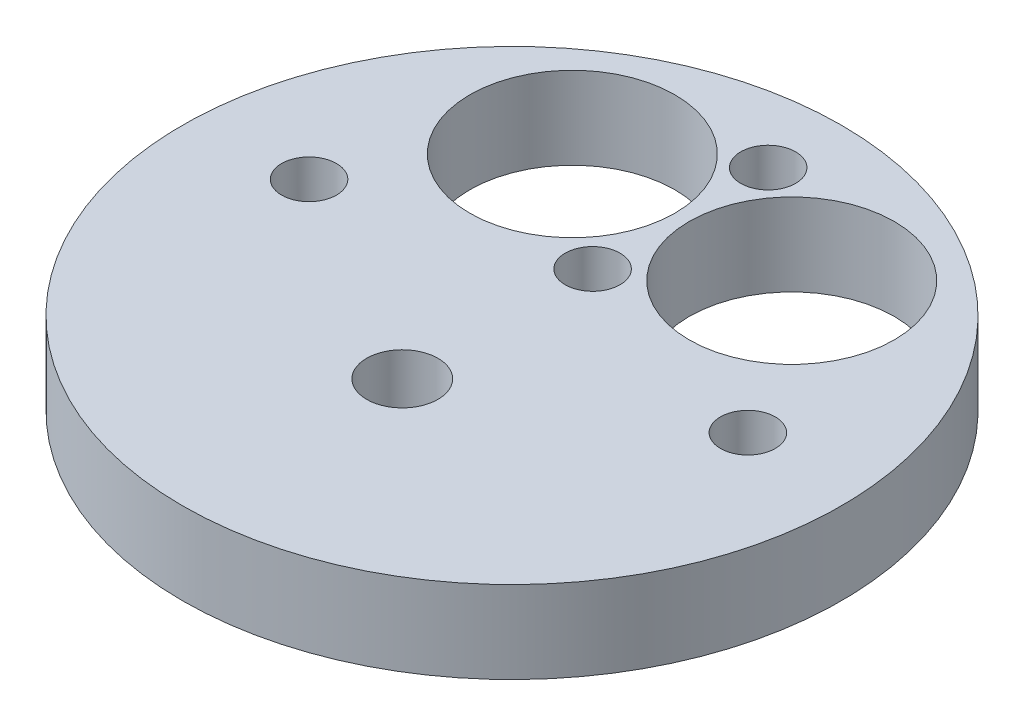
SolidWorks part; units mm, degrees
ref_plane "Front Plane" through (0, 0, 0) normal (0, 0, 1) x (1, 0, 0)
ref_plane "Top Plane" through (0, 0, 0) normal (0, 1, 0) x (1, 0, 0)
ref_plane "Right Plane" through (0, 0, 0) normal (1, 0, 0) x (0, 0, -1)
sketch "Sketch1" plane through (0, 0, 0) normal (0, 1, 0) x (1, 0, 0)
  circle A0 centre (0, 0) radius 38.1508
extrude "Boss-Extrude1" add sketch "Sketch1" along normal blind 9.525
sketch "Sketch2" plane through (0, 9.525, 0) normal (0, 1, 0) x (1, 0, 0)
  line L0 (-38.1508, 0) -> (38.1508, 0) construction
  line L1 (0, 38.1508) -> (0, -38.1508) construction
  line L2 (0, 0) -> (26.9767, -26.9767) construction
  line L3 (0, 0) -> (-26.9767, 26.9767) construction
  line L4 (-26.9767, 26.9767) -> (26.9767, 26.9767) construction
  line L5 (26.9767, 26.9767) -> (-26.9767, -26.9767) construction
  line L6 (-26.9767, -26.9767) -> (26.9767, -26.9767) construction
  line L7 (26.9767, -26.9767) -> (26.9767, 26.9767) construction
  line L8 (-26.9767, 26.9767) -> (-26.9767, -26.9767) construction
  circle A0 centre (0, 0) radius 38.1508 construction
sketch "Sketch5" plane through (0, 9.525, 0) normal (0, 1, 0) x (1, 0, 0)
  circle A0 centre (12.7, 15.875) radius 11.8745
  circle A1 centre (-12.7, 15.875) radius 11.8745
sketch "Sketch6" plane through (0, 9.525, 0) normal (0, 1, 0) x (1, 0, 0)
  circle A0 centre (0, 0) radius 36.5125 construction
sketch "Sketch9" plane through (0, 9.525, 0) normal (0, 1, 0) x (1, 0, 0)
  circle A2 centre (0, 26.0223) radius 3.175
  circle A3 centre (0, 5.7277) radius 3.175
sketch "Sketch10" plane through (0, 9.525, 0) normal (0, 1, 0) x (1, 0, 0)
  line L2 (-12.7, 33.655) -> (12.7, 33.655) construction
  line L3 (-12.7, 5.715) -> (12.7, 5.715) construction
  arc A6 (-12.7, 33.655) -> (-12.7, 5.715) centre (-12.7, 19.685) ccw construction
  arc A14 (12.7, 5.715) -> (12.7, 33.655) centre (12.7, 19.685) ccw construction
sketch "Sketch16" plane through (0, 0, 0) normal (0, -1, 0) x (1, 0, 0)
  circle A0 centre (0, 0) radius 36.5125
  dimension "D1" = 73.025
sketch "Sketch18" plane through (0, 9.525, 0) normal (0, 1, 0) x (1, 0, 0)
  line L0 (0, 1.905) -> (25.4, 1.905) construction
  line L1 (0, 38.1508) -> (0, -38.1508) construction
  line L2 (0, 1.905) -> (0, -20.1363) construction
  line L3 (-38.1508, 0) -> (38.1508, 0) construction
  circle A0 centre (25.4, 1.905) radius 3.175
  circle A1 centre (-25.4, 1.905) radius 3.175
  dimension "D1" = 1.905
  dimension "D2" = 25.4
sketch "Sketch19" plane through (0, 9.525, 0) normal (0, 1, 0) x (1, 0, 0)
  line L0 (0, 19.494) -> (0, 29.654) construction
  line L1 (0, 38.1508) -> (0, -38.1508) construction
  line L2 (0, 19.494) -> (0, 9.334) construction
  circle A0 centre (-12.7, 19.685) radius 11.8745
  circle A1 centre (12.7, 19.685) radius 11.8745
  circle A2 centre (0, 29.654) radius 3.175
  circle A3 centre (0, 9.334) radius 3.175
extrude "Cut-Extrude1" cut sketch "Sketch19" against normal blind 16.764
extrude "Cut-Extrude2" cut sketch "Sketch18" against normal blind 16.764
sketch "Sketch20" plane through (0, 9.525, 0) normal (0, 1, 0) x (1, 0, 0)
  circle A0 centre (-25.4, 1.905) radius 8.001 construction
  circle A1 centre (25.4, 1.905) radius 8.001 construction
ref_axis "Axis1" through (0, -3.81, 0) along (0, 1, 0)
sketch "Sketch21" plane through (0, 9.525, 0) normal (0, 1, 0) x (1, 0, 0)
  line L0 (0, 38.1508) -> (0, -38.1508) construction
  circle A0 centre (0, -12.7) radius 4.1275
  dimension "D2" = 8.255
  dimension "D1" = 12.7
extrude "Cut-Extrude3" cut sketch "Sketch21" against normal through all
